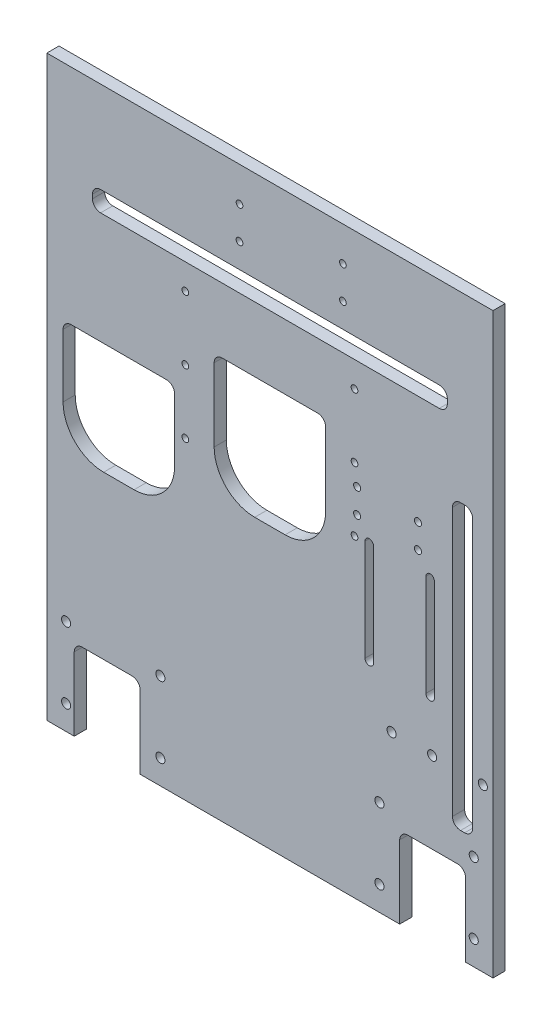
SolidWorks part; units mm, degrees
ref_plane "Front" through (0, 0, 0) normal (0, 0, 1) x (1, 0, 0)
ref_plane "Top" through (0, 0, 0) normal (0, 1, 0) x (1, 0, 0)
ref_plane "Right" through (0, 0, 0) normal (1, 0, 0) x (0, 0, -1)
sketch "Esquisse1" plane through (0, 0, 0) normal (0, 0, 1) x (1, 0, 0)
  line L1 (0, 0) -> (220, 0)
  line L2 (0, 0) -> (0, 285)
  line L3 (0, 285) -> (220, 285)
  line L4 (220, 0) -> (220, 285)
  dimension "D1" = 220
  dimension "D2" = 285
extrude "Boss.-Extru.1" add sketch "Esquisse1" along normal blind 6
sketch "Esquisse2" plane through (0, 0, 0) normal (0, -1, 0) x (1, 0, 0)
  line L0 (0, 3) -> (220, 3) construction
  line L1 (0, 6) -> (0, 0) construction
  line L2 (220, 6) -> (220, 0) construction
  line L3 (110, 3) -> (110, 28.0559) construction
  circle A0 centre (110, 3) radius 2
  circle A1 centre (213, 3) radius 2
  circle A2 centre (7, 3) radius 2
  dimension "D1" = 4
  dimension "D2" = 103
extrude "Enlèv. mat.-Extru.1" cut sketch "Esquisse2" against normal blind 8
sketch "Esquisse3" plane through (0, 0, 6) normal (0, 0, 1) x (1, 0, 0)
  line L0 (110, 0) -> (110, 285) construction
  line L1 (0, 0) -> (220, 0) construction
  line L2 (220, 285) -> (0, 285) construction
  line L3 (82.5, 198) -> (137.5, 198)
  line L4 (137.5, 198) -> (137.5, 138)
  line L5 (137.5, 138) -> (82.5, 138)
  line L6 (82.5, 198) -> (82.5, 138)
  line L8 (8, 175) -> (63, 175)
  line L9 (8, 175) -> (8, 120)
  line L10 (8, 120) -> (63, 120)
  line L11 (63, 175) -> (63, 120)
  line L12 (200, 55) -> (210, 55)
  line L13 (200, 55) -> (200, 195)
  line L14 (200, 195) -> (210, 195)
  line L15 (210, 55) -> (210, 195)
  point P11 (110, 138)
  point P12 (110, 198)
  dimension "D1" = 60
  dimension "D2" = 55
  dimension "D3" = 138
  dimension "D4" = 55
  dimension "D5" = 47
  dimension "D6" = 55
  dimension "D7" = 120
  dimension "D8" = 140
  dimension "D9" = 55
  dimension "D10" = 90
  dimension "D11" = 10
extrude "Enlèv. mat.-Extru.2" cut sketch "Esquisse3" against normal through all both and the other way through all
sketch "Esquisse5" plane through (0, 0, 6) normal (0, 0, 1) x (1, 0, 0)
  line L0 (110, 230) -> (110, 0) construction
  line L1 (22.5, 240) -> (197.5, 240)
  line L2 (22.5, 240) -> (22.5, 230)
  line L3 (22.5, 230) -> (197.5, 230)
  line L4 (197.5, 240) -> (197.5, 230)
  line L5 (0, 0) -> (220, 0) construction
  dimension "D1" = 175
  dimension "D2" = 10
  dimension "D3" = 230
extrude "Enlèv. mat.-Extru.3" cut sketch "Esquisse5" against normal through all both and the other way through all
sketch "Esquisse6" plane through (0, 0, 6) normal (0, 0, 1) x (1, 0, 0)
  line L0 (170, 80) -> (190, 80) construction
  line L1 (0, 0) -> (220, 0) construction
  line L2 (137.5, 138) -> (82.5, 138) construction
  line L3 (215, 80) -> (190, 80) construction
  line L4 (168, 193.9299) -> (168, 170.25) construction
  line L5 (186.4274, 170.25) -> (149.5726, 170.25) construction
  line L6 (0, 285) -> (0, 0) construction
  circle A0 centre (190, 80) radius 2.25
  circle A1 centre (170, 80) radius 2.25
  circle A2 centre (215, 80) radius 2.25
  circle A3 centre (153, 176.25) radius 1.75
  circle A4 centre (183, 176.25) radius 1.75
  circle A5 centre (183, 164.25) radius 1.75
  circle A6 centre (153, 164.25) radius 1.75
  point P8 (110, 138)
  dimension "D1" = 4.5
  dimension "D3" = 80
  dimension "D6" = 30
  dimension "D7" = 12
  dimension "D8" = 3.5
  dimension "D2" = 20
  dimension "D4" = 60
  dimension "D5" = 25
  dimension "D9" = 168
  dimension "D10" = 170.25
extrude "Enlèv. mat.-Extru.4" cut sketch "Esquisse6" against normal through all both and the other way through all
sketch "Esquisse7" plane through (0, 0, 6) normal (0, 0, 1) x (1, 0, 0)
  line L0 (110, 0) -> (110, 285) construction
  line L1 (0, 0) -> (220, 0) construction
  line L2 (220, 285) -> (0, 285) construction
  line L3 (68.285, 186) -> (68.285, 217.4) construction
  line L4 (68.285, 186) -> (110, 186) construction
  line L5 (151.715, 186) -> (151.715, 217.4) construction
  line L6 (95, 268) -> (120.5, 268) construction
  line L7 (120.5, 268) -> (120.5, 260) construction
  line L8 (120.5, 260) -> (137.9818, 260) construction
  line L9 (95, 252) -> (120.5, 252) construction
  line L10 (22.5, 240) -> (197.5, 240) construction
  circle A0 centre (68.285, 217.4) radius 1.65
  circle A1 centre (68.285, 186) radius 1.65
  circle A2 centre (68.285, 154.6) radius 1.65
  circle A3 centre (151.715, 154.6) radius 1.65
  circle A4 centre (151.715, 186) radius 1.65
  circle A5 centre (151.715, 217.4) radius 1.65
  circle A6 centre (95, 268) radius 1.65
  circle A7 centre (146, 268) radius 1.65
  circle A8 centre (146, 252) radius 1.65
  circle A9 centre (95, 252) radius 1.65
  point P33 (122.2858, 252)
  point P34 (134.9671, 260)
  point P35 (137.9818, 260)
  dimension "D1" = 31.4
  dimension "D2" = 3.3
  dimension "D5" = 16
  dimension "D6" = 51
  dimension "D9" = 3.3
  dimension "D7" = 15
  dimension "D3" = 83.43
  dimension "D4" = 186
  dimension "D8" = 20
extrude "Enlèv. mat.-Extru.5" cut sketch "Esquisse7" against normal through all both and the other way through all
sketch "Esquisse8" plane through (0, 0, 6) normal (0, 0, 1) x (1, 0, 0)
  line L0 (110, 0) -> (110, 285) construction
  line L1 (0, 0) -> (220, 0) construction
  line L2 (220, 285) -> (0, 285) construction
  line L3 (174, 0) -> (174, 40)
  line L4 (13.5, 0) -> (46, 0)
  line L5 (13.5, 0) -> (13.5, 40)
  line L6 (13.5, 40) -> (46, 40)
  line L7 (46, 0) -> (46, 40)
  line L8 (206.5, 40) -> (174, 40)
  line L9 (206.5, 0) -> (206.5, 40)
  line L10 (206.5, 0) -> (174, 0)
  dimension "D1" = 128
  dimension "D2" = 32.5
  dimension "D3" = 40
extrude "Enlèv. mat.-Extru.6" cut sketch "Esquisse8" against normal through all both and the other way through all
fillet "Congé1" radius 20 4 edges at (137.5, 138, 3) (82.5, 138, 3) (63, 120, 3) (8, 120, 3)
fillet "Congé2" radius 4 16 edges at (137.5, 198, 3) (82.5, 198, 3) (197.5, 230, 3) (197.5, 240, 3) (22.5, 240, 3) (22.5, 230, 3) (63, 175, 3) (8, 175, 3) (200, 195, 3) (210, 195, 3) (210, 55, 3) (200, 55, 3) (206.5, 40, 3) (174, 40, 3) (46, 40, 3) (13.5, 40, 3)
sketch "Esquisse9" plane through (0, 0, 6) normal (0, 0, 1) x (1, 0, 0)
  line L0 (189, 155) -> (189, 105) construction
  line L1 (191.1, 155) -> (191.1, 105)
  line L2 (186.9, 155) -> (186.9, 105)
  line L3 (189, 130) -> (159, 130) construction
  line L4 (174, 130) -> (174, 131.5076) construction
  line L5 (159, 105) -> (159, 155) construction
  line L6 (156.9, 105) -> (156.9, 155)
  line L7 (161.1, 105) -> (161.1, 155)
  line L9 (206, 55) -> (204, 55) construction
  line L10 (200, 59) -> (200, 191) construction
  arc A0 (191.1, 155) -> (186.9, 155) centre (189, 155) ccw
  arc A1 (186.9, 105) -> (191.1, 105) centre (189, 105) ccw
  arc A2 (156.9, 105) -> (161.1, 105) centre (159, 105) ccw
  arc A3 (161.1, 155) -> (156.9, 155) centre (159, 155) ccw
  point P2 (189, 130)
  point P13 (159, 130)
  dimension "D1" = 4.2
  dimension "D2" = 30
  dimension "D3" = 11
  dimension "D4" = 50
  dimension "D5" = 50
extrude "Enlèv. mat.-Extru.7" cut sketch "Esquisse9" against normal through all both and the other way through all
sketch "Esquisse10" plane through (0, 0, 6) normal (0, 0, 1) x (1, 0, 0)
  line L0 (9.5, 0) -> (9.5, 52.9697) construction
  line L1 (0, 0) -> (13.5, 0) construction
  line L2 (0, 285) -> (0, 0) construction
  line L3 (110, 0) -> (110, 48.9194) construction
  line L4 (46, 0) -> (174, 0) construction
  line L5 (32.75, 0) -> (32.75, 52.9697) construction
  circle A0 centre (9.5, 12) radius 2.25
  circle A1 centre (9.5, 47) radius 2.25
  circle A2 centre (210.5, 47) radius 2.25
  circle A3 centre (210.5, 12) radius 2.25
  circle A4 centre (56, 47) radius 2.25
  circle A5 centre (56, 12) radius 2.25
  circle A6 centre (164, 12) radius 2.25
  circle A7 centre (164, 47) radius 2.25
  dimension "D2" = 4.5
  dimension "D3" = 35
  dimension "D4" = 12
  dimension "D5" = 46.5
  dimension "D1" = 9.5
extrude "Enlèv. mat.-Extru.8" cut sketch "Esquisse10" against normal through all both and the other way through all
